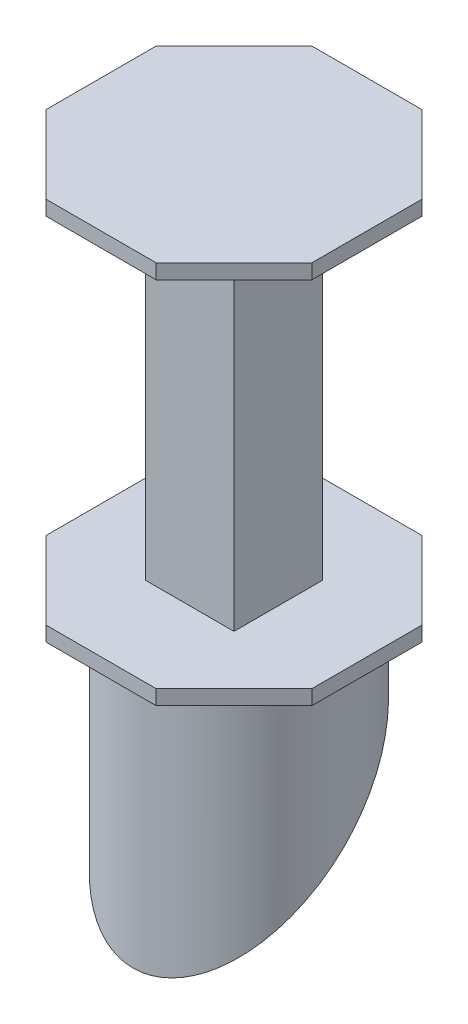
SolidWorks part; units mm, degrees
ref_plane "Front Plane" through (0, 0, 0) normal (0, 0, 1) x (1, 0, 0)
ref_plane "Top Plane" through (0, 0, 0) normal (0, 1, 0) x (1, 0, 0)
ref_plane "Right Plane" through (0, 0, 0) normal (1, 0, 0) x (0, 0, -1)
sketch "Sketch2" plane through (0, 0, 0) normal (1, 0, 0) x (0, 0, -1)
  line L0 (1.0414, 1052.7211) -> (1.0414, 994.4816) construction
  line L1 (1.0414, 1052.7211) -> (-21.7283, 1052.7211)
  line L2 (-21.7283, 1052.7211) -> (-21.7283, 994.4816)
  line L3 (-21.7283, 994.4816) -> (1.0414, 994.4816)
  line L4 (1.0414, 1052.7211) -> (1.0414, 994.4816)
revolve "Revolve1" add sketch "Sketch2" angle 360 about L0
sketch "Sketch3" plane through (0, 0, 0) normal (1, 0, 0) x (0, 0, -1)
  line L0 (-21.7283, 994.4816) -> (23.8111, 1040.0211)
  line L1 (23.8111, 1040.0211) -> (23.8111, 994.4816)
  line L2 (23.8111, 994.4816) -> (-21.7283, 994.4816)
extrude "Cut-Extrude1" cut sketch "Sketch3" against normal through all both and the other way through all
shell "Shell1" thickness 3.175 removed face at (0, 1040.0211, -23.8111)
sketch "Sketch4" plane through (0, 1052.7211, 0) normal (0, 1, 0) x (1, 0, 0)
  line L4 (28.575, 11.8362) -> (11.8362, 28.575)
  line L5 (11.8362, 28.575) -> (-11.8362, 28.575)
  line L6 (-11.8362, 28.575) -> (-28.575, 11.8362)
  line L7 (-28.575, 11.8362) -> (-28.575, -11.8362)
  line L8 (-28.575, -11.8362) -> (-11.8362, -28.575)
  line L9 (-11.8362, -28.575) -> (11.8362, -28.575)
  line L10 (11.8362, -28.575) -> (28.575, -11.8362)
  line L11 (28.575, -11.8362) -> (28.575, 11.8362)
  circle A0 centre (0, 0) radius 28.575 construction
  dimension "D1" = 57.15
extrude "Boss-Extrude1" add sketch "Sketch4" along normal blind 3.175
sketch "Sketch5" plane through (0, 1055.8961, 0) normal (0, 1, 0) x (1, 0, 0)
  line L1 (9.525, 9.525) -> (-9.525, 9.525)
  line L2 (9.525, 9.525) -> (9.525, -9.525)
  line L3 (9.525, -9.525) -> (-9.525, -9.525)
  line L4 (-9.525, 9.525) -> (-9.525, -9.525)
  line L5 (0, -9.525) -> (0, 9.525) construction
  line L6 (9.525, 0) -> (-9.525, 0) construction
  point P0 (0, 0)
  dimension "D1" = 19.05
extrude "Boss-Extrude2" add sketch "Sketch5" along normal blind 76.2
sketch "Sketch6" plane through (0, 1132.0961, 0) normal (0, 1, 0) x (1, 0, 0)
  line L0 (-11.8362, 28.575) -> (-28.575, 11.8362) construction
  line L1 (-28.575, -11.8362) -> (-11.8362, -28.575)
  line L2 (-11.8362, -28.575) -> (11.8362, -28.575)
  line L3 (11.8362, -28.575) -> (28.575, -11.8362)
  line L4 (28.575, -11.8362) -> (28.575, 11.8362)
  line L5 (28.575, 11.8362) -> (11.8362, 28.575)
  line L6 (11.8362, 28.575) -> (-11.8362, 28.575)
  line L7 (-11.8362, 28.575) -> (-28.575, 11.8362)
  line L8 (-28.575, 11.8362) -> (-28.575, -11.8362)
  circle A0 centre (0, 0) radius 28.575 construction
extrude "Boss-Extrude3" add sketch "Sketch6" along normal blind 3.175
